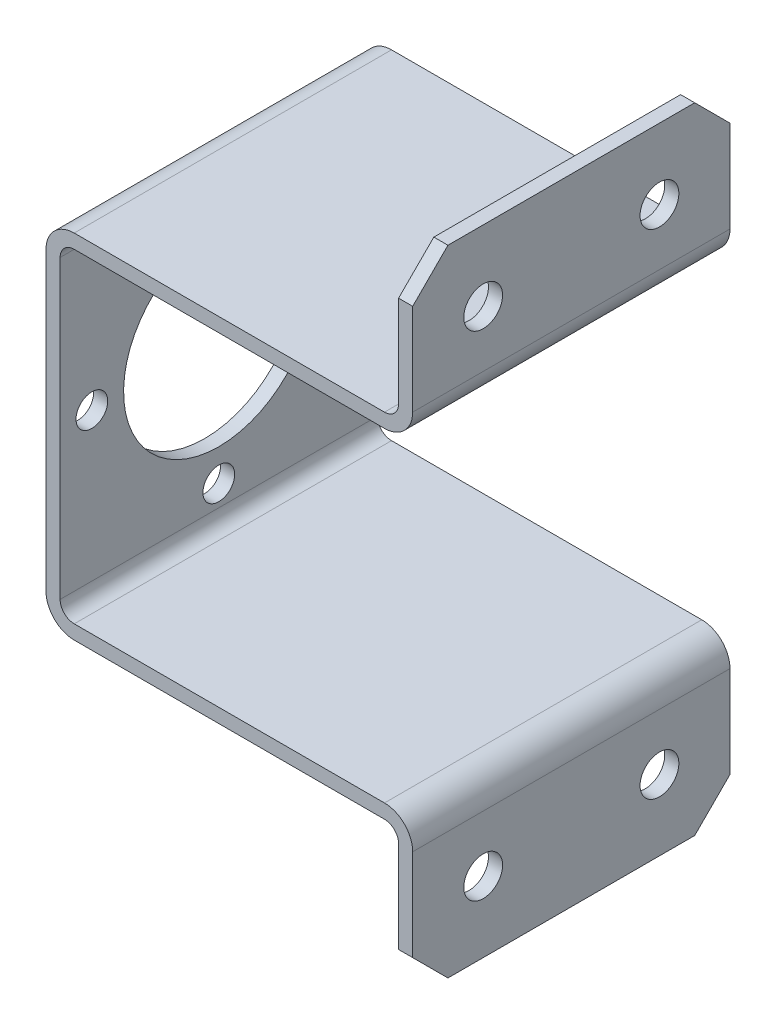
SolidWorks part; units mm, degrees
material "3.0205 (EN AW-1200)"
ref_plane "Plan de face" through (0, 0, 0) normal (0, 0, 1) x (1, 0, 0)
ref_plane "Plan de dessus" through (0, 0, 0) normal (0, 1, 0) x (1, 0, 0)
ref_plane "Plan de droite" through (0, 0, 0) normal (1, 0, 0) x (0, 0, -1)
sketch "Esquisse1" plane through (0, 0, 0) normal (0, 0, 1) x (1, 0, 0)
  line L0 (52, 70) -> (50, 70)
  line L1 (50, 70) -> (50, 50)
  line L2 (50, 50) -> (0, 50)
  line L3 (0, 50) -> (0, 0)
  line L4 (0, 0) -> (50, 0)
  line L5 (50, 0) -> (50, -20)
  line L6 (50, -20) -> (52, -20)
  line L7 (52, -20) -> (52, 2)
  line L8 (52, 2) -> (2, 2)
  line L9 (2, 2) -> (2, 48)
  line L10 (2, 48) -> (52, 48)
  line L11 (52, 48) -> (52, 70)
  dimension "D1" = 2
  dimension "D2" = 2
  dimension "D3" = 2
  dimension "D4" = 2
  dimension "D5" = 2
  dimension "D6" = 50
  dimension "D7" = 50
  dimension "D8" = 20
extrude "Boss.-Extru.1" add sketch "Esquisse1" along normal mid plane 45
hole_wizard "Dégagement M51" positions "Esquisse3" profile "Esquisse2" hole size "M5" standard "Ansi Métrique" end condition up to next
sketch "Esquisse3" plane through (50, 0, 0) normal (-1, 0, 0) x (0, 0, 1)
  line L0 (22.5, -20) -> (-22.5, -20) construction
  line L1 (22.5, 0) -> (22.5, -20) construction
  line L2 (-22.5, 0) -> (-22.5, -20) construction
  line L3 (22.5, 70) -> (22.5, 50) construction
  line L5 (22.5, 70) -> (-22.5, 70) construction
  line L6 (-22.5, 70) -> (-22.5, 50) construction
  point P0 (12.5, 60)
  point P1 (-12.5, 60)
  point P3 (-12.5, -10)
  point P5 (12.5, -10)
  dimension "D1" = 10
  dimension "D2" = 10
  dimension "D3" = 10
  dimension "D4" = 10
  dimension "D5" = 10
  dimension "D6" = 10
  dimension "D7" = 10
  dimension "D8" = 10
sketch "Esquisse2" plane through (50, 60, 12.5) normal (0, 1, 0) x (0, 0, 1)
  line L0 (0, 0) -> (0, 2)
  line L1 (0, 2) -> (2.75, 2)
  line L2 (2.75, 2) -> (2.75, 0)
  line L5 (2.75, 0) -> (0, 0)
  line L11 (0, -6.35) -> (0, 107.95) construction
  dimension "Diamètre du perçage jusqu'au prochain" = 5.5
  dimension "Profondeur du perçage jusqu'au prochain" = 2
ref_point "Point1"
ref_point "Point3"
ref_point "Point4"
ref_axis "Axe4" through (0, 25, 0) along (0, -1, 0)
ref_axis "Axe5" through (2, 25, 0) along (-1, 0, 0)
sketch "Esquisse11" plane through (0, 0, 0) normal (-1, 0, 0) x (0, 0, 1)
  line L0 (0, 25) -> (0, 2.8015) construction
  circle A0 centre (0, 25) radius 18
  point P2 (0, 7)
  dimension "D1" = 36
hole_wizard "Dégagement M42" positions "Esquisse13" profile "Esquisse12" hole size "M4" standard "Ansi Métrique" end condition up to next
sketch "Esquisse13" plane through (0, 0, 0) normal (-1, 0, 0) x (0, 0, 1)
  point P0 (0, 7)
sketch "Esquisse12" plane through (0, 7, 0) normal (0, 1, 0) x (0, 0, 1)
  line L0 (0, 0) -> (0, 2.001)
  line L1 (0, 2.001) -> (2.25, 2.001)
  line L2 (2.25, 2.001) -> (2.25, 0)
  line L5 (2.25, 0) -> (0, 0)
  line L11 (0, -6.35) -> (0, 107.95) construction
  dimension "Diamètre du perçage jusqu'au prochain" = 4.5
  dimension "Profondeur du perçage jusqu'au prochain" = 2.001
pattern_circular "Répétition circulaire2" count 4 over 360 about axis through (2, 25, 0) along (-1, 0, 0) of "Dégagement M42"
fillet "Congé1" radius 2 4 edges at (2, 2, 0) (2, 48, 0) (50, 50, 0) (50, 0, 0)
chamfer "Chanfrein1" distance 5 angle 45 4 edges at (51, 70, -22.5) (51, 70, 22.5) (51, -20, 22.5) (51, -20, -22.5)
fillet "Congé2" radius 4 4 edges at (0, 50, 0) (0, 0, 0) (52, 2, 0) (52, 48, 0)
ref_plane "Plan1" through (0, 25, 0) normal (0, 1, 0) x (-1, 0, 0)
ref_plane "Plan2" through (0, 0, 0) normal (0, 0, 1) x (1, 0, 0)
sketch "Esquisse15" plane through (0, 0, 0) normal (-1, 0, 0) x (0, 0, 1)
  line L0 (0, -39.9121) -> (0, 39.9121) construction
  line L1 (37.6706, 25) -> (-37.6706, 25) construction
  point P0 (0, 25)
sketch "Esquisse16" plane through (0, 0, 0) normal (-1, 0, 0) x (0, 0, 1)
  circle A0 centre (0, 25) radius 13.5
  dimension "D1" = 27
extrude "Enlèv. mat.-Extru.1" cut sketch "Esquisse16" against normal up to next
